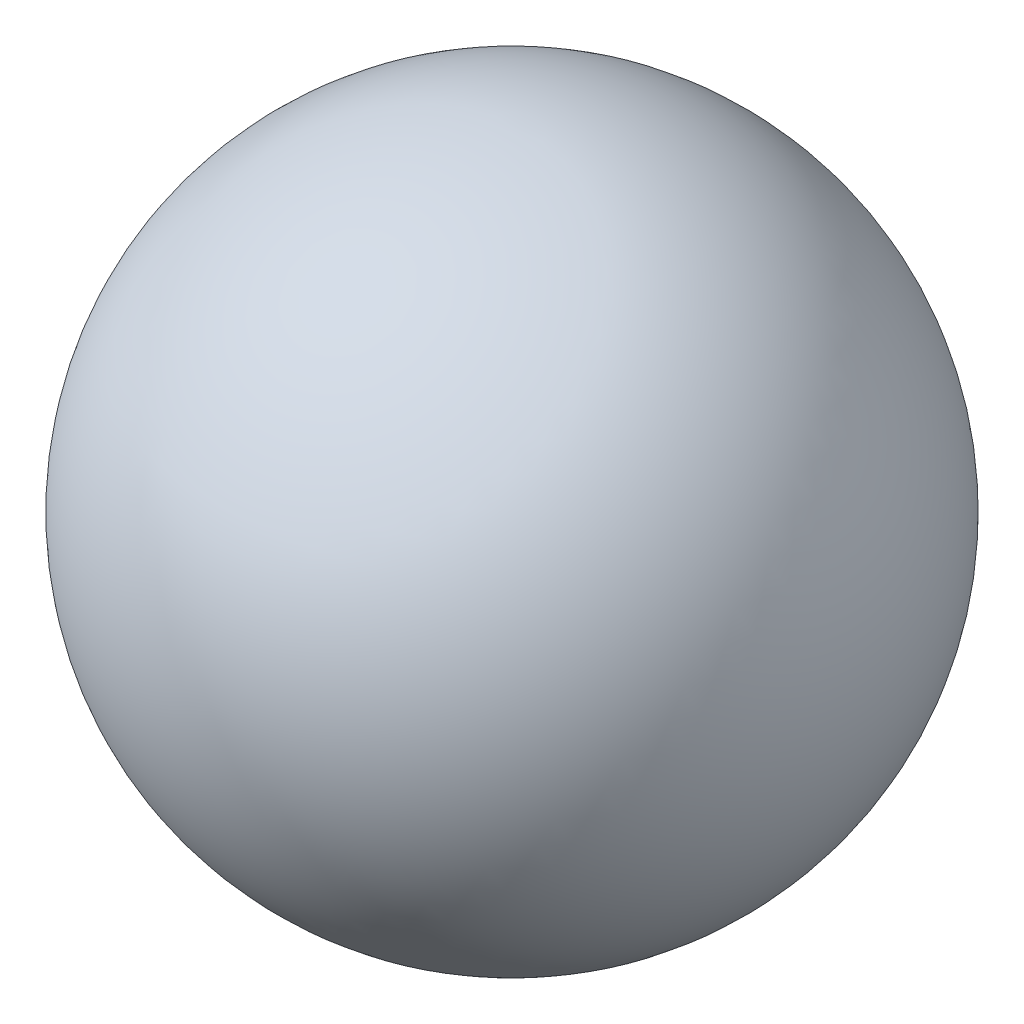
SolidWorks part; units mm, degrees
ref_plane "Front Plane" through (0, 0, 0) normal (0, 0, 1) x (1, 0, 0)
ref_plane "Top Plane" through (0, 0, 0) normal (0, 1, 0) x (1, 0, 0)
ref_plane "Right Plane" through (0, 0, 0) normal (1, 0, 0) x (0, 0, -1)
sketch "Sketch1" plane through (0, 0, 0) normal (0, 0, 1) x (1, 0, 0)
  line L0 (0, 28.5492) -> (0, -25.1763) construction
  line L1 (0, -21) -> (0, 21)
  arc A0 (0, -21) -> (0, 21) centre (0, 0) ccw
  dimension "D1" = 42
revolve "Revolve2" add sketch "Sketch1" angle 360 about L1
